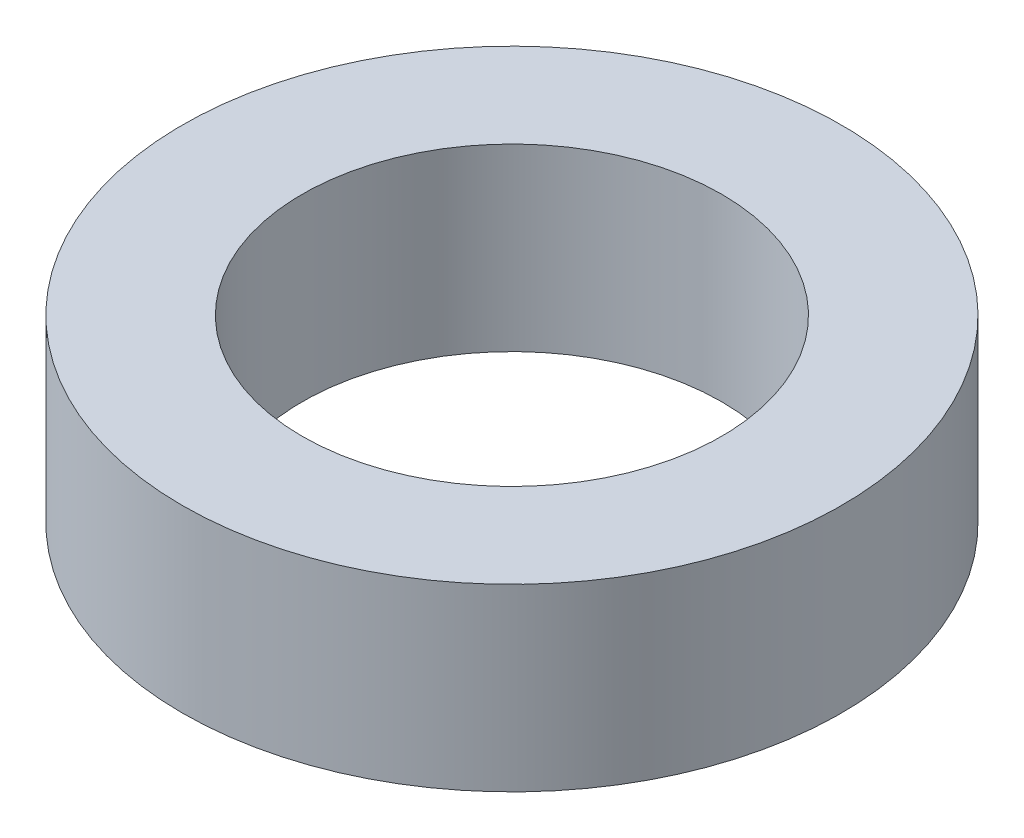
SolidWorks part; units mm, degrees
ref_plane "Front Plane" through (0, 0, 0) normal (0, 0, 1) x (1, 0, 0)
ref_plane "Top Plane" through (0, 0, 0) normal (0, 1, 0) x (1, 0, 0)
ref_plane "Right Plane" through (0, 0, 0) normal (1, 0, 0) x (0, 0, -1)
sketch "Sketch1" plane through (0, 0, 0) normal (0, 1, 0) x (1, 0, 0)
  circle A0 centre (0, 0) radius 27.5
  dimension "FLANGE_OD" = 55
extrude "Boss-Extrude1" add sketch "Sketch1" along normal blind 15
sketch "Sketch2" plane through (0, 0, 0) normal (0, 1, 0) x (1, 0, 0)
  circle A0 centre (0, 0) radius 17.5
  dimension "BORE_D" = 35
extrude "Cut-Extrude1" cut sketch "Sketch2" along normal through all
sketch "Sketch3" plane through (0, 15, 0) normal (0, 1, 0) x (1, 0, 0)
  circle A0 centre (0, 0) radius 10.0818 construction
  circle A1 centre (-10.0818, 0) radius 1.542
  dimension "BOLT_D" = 3.0839
  dimension "BOLT_PCD" = 20.1635
extrude "Cut-Extrude2" cut sketch "Sketch3" against normal blind 14.7653 rebuild error yes
pattern_circular "CirPattern1" count 6 over 360 rebuild error yes
